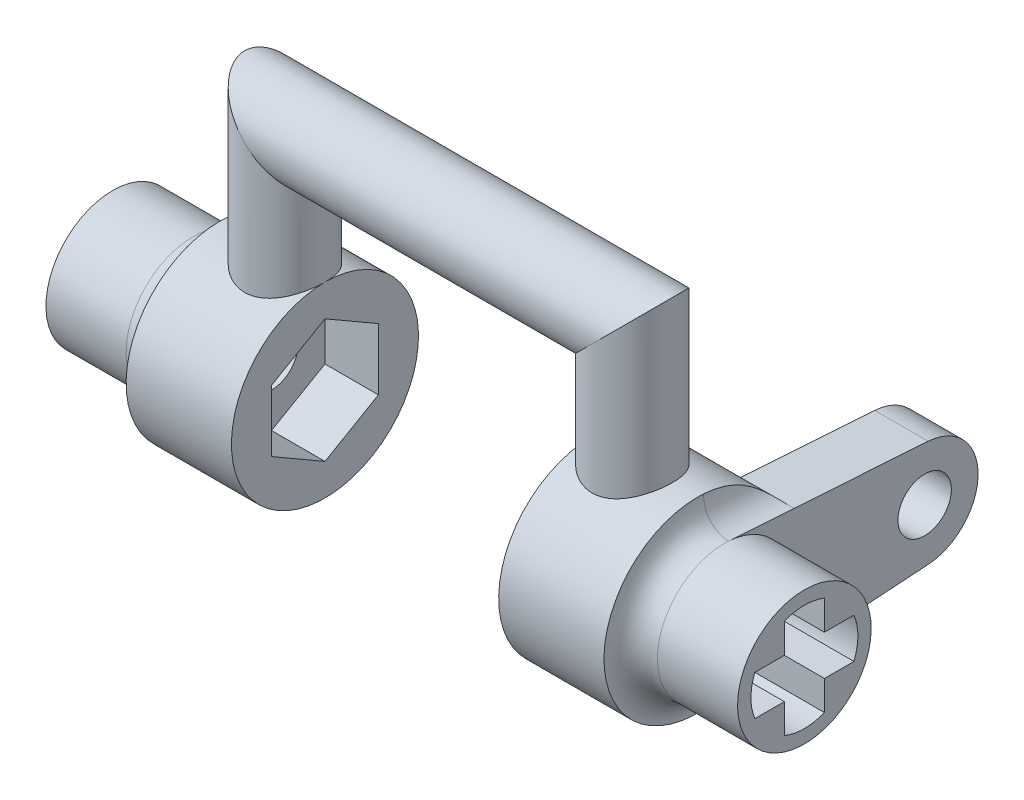
SolidWorks part; units mm, degrees
ref_plane "前视基准面" through (0, 0, 0) normal (0, 0, 1) x (1, 0, 0)
ref_plane "上视基准面" through (0, 0, 0) normal (0, 1, 0) x (1, 0, 0)
ref_plane "右视基准面" through (0, 0, 0) normal (1, 0, 0) x (0, 0, -1)
other "Configuration Table"
sketch "草图1" plane through (0, 0, 0) normal (0, 0, 1) x (1, 0, 0)
  line L0 (-210.8221, 0) -> (10330.2839, 0) construction
  line L1 (0, 0) -> (0, 8) construction
  line L2 (-6.5, 8) -> (6.5, 8)
  line L3 (6.5, 8) -> (6.5, 0)
  line L4 (6.5, 0) -> (9.5, 0)
  line L5 (-6.5, 8) -> (-6.5, 0)
  line L6 (-6.5, 0) -> (-9.5, 0)
  point P8 (0, 8)
  dimension "D1" = 8
  dimension "D2" = 13
  dimension "D3" = 3
  dimension "D4" = 3
sweep "扫描1" add path "草图1" circular profile diameter 3 parameters "D3"=3
sketch "草图8" plane through (0, 0, 0) normal (1, 0, 0) x (0, 0, -1)
  circle A0 centre (0, 0) radius 2.5
  dimension "D1" = 5
extrude "凸台-拉伸1" add sketch "草图8" along normal blind 3.44 and the other way blind 4.5 from surface starting at face at (9.5, 1.5, 0)
sketch "草图9" plane through (0, 0, 0) normal (1, 0, 0) x (0, 0, -1)
  circle A1 centre (0, 0) radius 2.5
  circle A2 centre (0, 0) radius 2.5
  dimension "D1" = 0
extrude "凸台-拉伸2" add sketch "草图9" against normal blind 3.44 and the other way blind 4.5 from surface starting at face at (-9.5, 1.5, 0)
ref_plane "基准面1" through (9.94, 0, 0) normal (1, 0, 0) x (0, 0, -1)
sketch "草图10" plane through (0, 0, 0) normal (1, 0, 0) x (0, 0, -1)
  line L0 (0.75, 0.75) -> (1.854, 0.75)
  line L1 (-1.854, 0.75) -> (-0.75, 0.75)
  line L3 (-1.854, -0.75) -> (-0.75, -0.75)
  line L5 (-1.854, 0.75) -> (1.854, -0.75) construction
  line L6 (-1.854, -0.75) -> (1.854, 0.75) construction
  line L8 (-0.75, -1.854) -> (-0.75, -0.75)
  line L10 (0.75, -1.854) -> (0.75, -0.75)
  line L11 (-0.75, -1.854) -> (0.75, 1.854) construction
  line L12 (-0.75, 1.854) -> (0.75, -1.854) construction
  line L13 (-0.75, 0.75) -> (-0.75, 1.854)
  line L14 (0.75, 0.75) -> (0.75, 1.854)
  line L16 (0.75, -0.75) -> (1.854, -0.75)
  arc A0 (-1.854, 0.75) -> (-1.854, -0.75) centre (0, 0) ccw
  arc A1 (-0.75, -1.854) -> (0.75, -1.854) centre (0, 0) ccw
  arc A2 (1.854, -0.75) -> (1.854, 0.75) centre (0, 0) ccw
  arc A3 (0.75, 1.854) -> (-0.75, 1.854) centre (0, 0) ccw
  dimension "D1" = 4
  dimension "D2" = 1.5
  dimension "D3" = 1.5
  dimension "D4" = 2.1213
  dimension "D5" = 1.104
sketch "草图14" plane through (0, 0, 0) normal (1, 0, 0) x (0, 0, -1)
  line L0 (-1000, 0) -> (49000, 0) construction
  line L1 (0.1667, 2.4944) -> (7.6333, 1.9956)
  line L2 (0.1667, -2.4944) -> (7.6333, -1.9956)
  arc A0 (7.6333, -1.9956) -> (7.6333, 1.9956) centre (7.5, 0) ccw
  circle A1 centre (0, 0) radius 2.5 construction
  circle A2 centre (7.5, 0) radius 1
  circle A3 centre (0, 0) radius 2.5
  arc A4 (0.1667, 2.4944) -> (0.1667, -2.4944) centre (0, 0) ccw
  dimension "D1" = 4
  dimension "D4" = 2
  dimension "D3" = 7.5
  dimension "D2" = 0
extrude "凸台-拉伸3" add sketch "草图14" against normal blind 2 from surface starting at plane "基准面1"
extrude "切除-拉伸1" cut sketch "草图10" against normal blind 4 from surface starting at face at (12.94, 2.5, 0)
sketch "草图11" plane through (0, 0, 0) normal (1, 0, 0) x (0, 0, -1)
  line L8 (0.75, 0.75) -> (0.75, 1.854)
  line L9 (-0.75, 1.854) -> (-0.75, 0.75)
  line L10 (-0.75, 0.75) -> (-1.854, 0.75)
  line L11 (-1.854, -0.75) -> (-0.75, -0.75)
  line L12 (-0.75, -0.75) -> (-0.75, -1.854)
  line L13 (0.75, -1.854) -> (0.75, -0.75)
  line L14 (0.75, -0.75) -> (1.854, -0.75)
  line L15 (1.854, 0.75) -> (0.75, 0.75)
  line L16 (0.75, 0.75) -> (0.75, 1.854)
  line L17 (-0.75, 1.854) -> (-0.75, 0.75)
  line L18 (-0.75, 0.75) -> (-1.854, 0.75)
  line L19 (-1.854, -0.75) -> (-0.75, -0.75)
  line L20 (-0.75, -0.75) -> (-0.75, -1.854)
  line L21 (0.75, -1.854) -> (0.75, -0.75)
  line L22 (0.75, -0.75) -> (1.854, -0.75)
  line L23 (1.854, 0.75) -> (0.75, 0.75)
  arc A4 (0.75, 1.854) -> (-0.75, 1.854) centre (0, 0) ccw
  arc A5 (-1.854, 0.75) -> (-1.854, -0.75) centre (0, 0) ccw
  arc A6 (-0.75, -1.854) -> (0.75, -1.854) centre (0, 0) ccw
  arc A7 (1.854, -0.75) -> (1.854, 0.75) centre (0, 0) ccw
  arc A8 (0.75, 1.854) -> (-0.75, 1.854) centre (0, 0) ccw
  arc A9 (-1.854, 0.75) -> (-1.854, -0.75) centre (0, 0) ccw
  arc A10 (-0.75, -1.854) -> (0.75, -1.854) centre (0, 0) ccw
  arc A11 (1.854, -0.75) -> (1.854, 0.75) centre (0, 0) ccw
  dimension "D1" = 0
extrude "切除-拉伸2" cut sketch "草图11" along normal blind 4 from surface starting at face at (-12.94, 2.5, 0)
sketch "草图16" plane through (0, 0, 0) normal (1, 0, 0) x (0, 0, -1)
  line L0 (0, 0) -> (0.75, 0) construction
  circle A0 centre (0.75, 0) radius 0.25
  dimension "D2" = 0.5
  dimension "D1" = 0.75
extrude "切除-拉伸3" cut sketch "草图16" along normal blind 0.25 from surface starting at face at (-8.94, 0, 0)
sketch "草图17" plane through (0, 0, 0) normal (1, 0, 0) x (0, 0, -1)
  circle A0 centre (0.75, 0) radius 0.25 construction
  circle A1 centre (0.75, 0) radius 0.25
extrude "切除-拉伸4" cut sketch "草图17" against normal blind 0.25 from surface starting at face at (8.94, 0, 0)
sketch "草图18" plane through (0, 0, 0) normal (1, 0, 0) x (0, 0, -1)
  circle A0 centre (0, 0) radius 3.5
  dimension "D1" = 7
extrude "凸台-拉伸4" add sketch "草图18" along normal up to surface (8.94 mm away) from surface up to face at (8.94, 0.25, -0.75) starting at face at (5, 2.5, 0)
sketch "草图20" plane through (0, 0, 0) normal (1, 0, 0) x (0, 0, -1)
  circle A0 centre (0, 0) radius 3.5
  dimension "D1" = 7
extrude "凸台-拉伸5" add sketch "草图20" along normal up to surface (-5 mm away) from surface up to face at (-5, 2.5, 0) starting at face at (-8.94, 0.25, -0.75)
sketch "草图25" plane through (0, 0, 0) normal (1, 0, 0) x (0, 0, -1)
  circle A0 centre (0, 0) radius 1
  dimension "D1" = 2
extrude "切除-拉伸6" cut sketch "草图25" against normal through all and the other way through all
fillet "圆角1" radius 1 4 edges at (-8.94, 2.5, 0) (8.94, 0, 2.5) (8.94, -2.4128, -1.3887) (8.94, 2.4128, -1.3887) first distance on face at (-12.94, 2.5, 0) first distance on face at (8.94, 0, 0.8057)
sketch "草图26" plane through (0, 0, 0) normal (1, 0, 0) x (0, 0, -1)
  line L1 (0, -2.3094) -> (2, -1.1547)
  line L2 (2, -1.1547) -> (2, 1.1547)
  line L3 (2, 1.1547) -> (0, 2.3094)
  line L4 (0, 2.3094) -> (-2, 1.1547)
  line L5 (-2, 1.1547) -> (-2, -1.1547)
  line L6 (-2, -1.1547) -> (0, -2.3094)
  circle A0 centre (0, 0) radius 2 construction
  dimension "D1" = 4
extrude "切除-拉伸7" cut sketch "草图26" against normal blind 2 from surface starting at face at (-5, 1, 0)
sketch "草图27" plane through (0, 0, 0) normal (1, 0, 0) x (0, 0, -1)
  line L6 (0, -2.3094) -> (2, -1.1547)
  line L7 (2, -1.1547) -> (2, 1.1547)
  line L8 (2, 1.1547) -> (0, 2.3094)
  line L9 (0, 2.3094) -> (-2, 1.1547)
  line L10 (-2, 1.1547) -> (-2, -1.1547)
  line L11 (-2, -1.1547) -> (0, -2.3094)
  line L12 (0, -2.3094) -> (2, -1.1547)
  line L13 (2, -1.1547) -> (2, 1.1547)
  line L14 (2, 1.1547) -> (0, 2.3094)
  line L15 (0, 2.3094) -> (-2, 1.1547)
  line L16 (-2, 1.1547) -> (-2, -1.1547)
  line L17 (-2, -1.1547) -> (0, -2.3094)
  dimension "D1" = 0
extrude "切除-拉伸8" cut sketch "草图27" along normal blind 2 from surface starting at face at (5, 1, 0)
